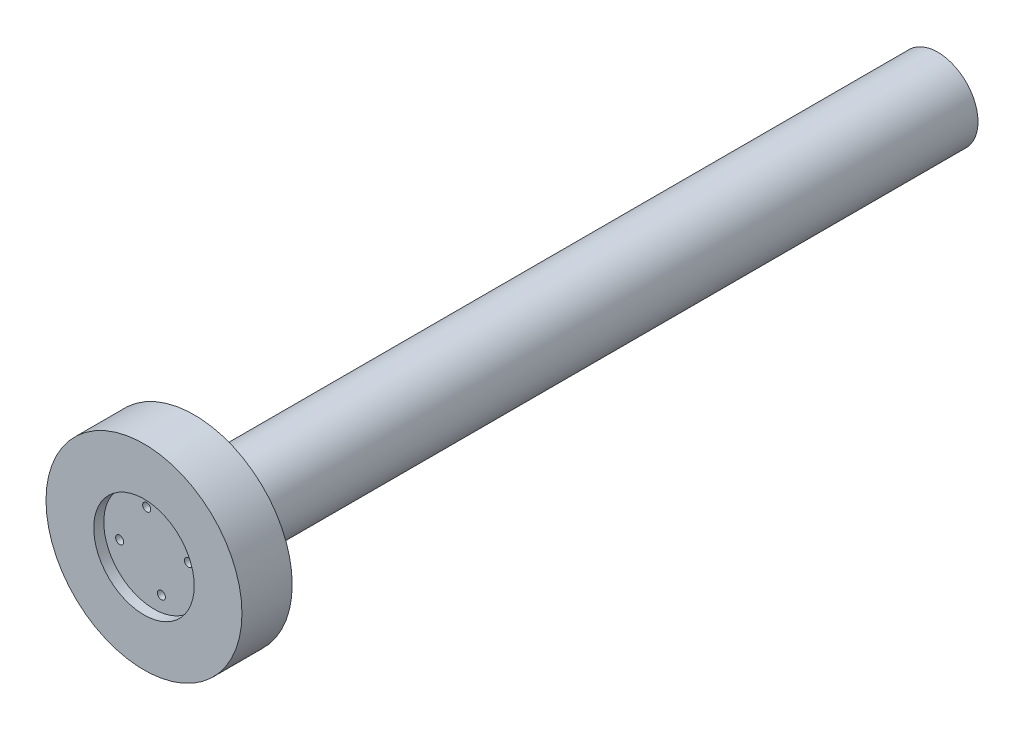
SolidWorks part; units mm, degrees
ref_plane "Front Plane" through (0, 0, 0) normal (0, 0, 1) x (1, 0, 0)
ref_plane "Top Plane" through (0, 0, 0) normal (0, 1, 0) x (1, 0, 0)
ref_plane "Right Plane" through (0, 0, 0) normal (1, 0, 0) x (0, 0, -1)
sketch "Sketch1" plane through (0, 0, 0) normal (0, 0, 1) x (1, 0, 0)
  circle A0 centre (0, 0) radius 8
  dimension "D1" = 16
extrude "Boss-Extrude1" add sketch "Sketch1" along normal blind 158
sketch "Sketch2" plane through (0, 0, 158) normal (0, 0, 1) x (1, 0, 0)
  circle A0 centre (0, 0) radius 19.5
extrude "Boss-Extrude2" add sketch "Sketch2" against normal blind 10
sketch "Sketch3" plane through (0, 0, 158) normal (0, 0, 1) x (1, 0, 0)
  circle A0 centre (0, 0) radius 10
  circle A1 centre (6.845, 1.4651) radius 0.8
  circle A2 centre (-1.4651, 6.845) radius 0.8
  circle A3 centre (-6.845, -1.4651) radius 0.8
  circle A4 centre (1.4651, -6.845) radius 0.8
extrude "Cut-Extrude1" cut sketch "Sketch3" against normal blind 2
extrude "Cut-Extrude2" cut sketch "Sketch3<2>" against normal blind 8 contours A2 | A3 | A4 | A1
sketch "Sketch3<2>" plane through (0, 0, 158) normal (0, 0, 1) x (1, 0, 0) same geometry as "Sketch3"
